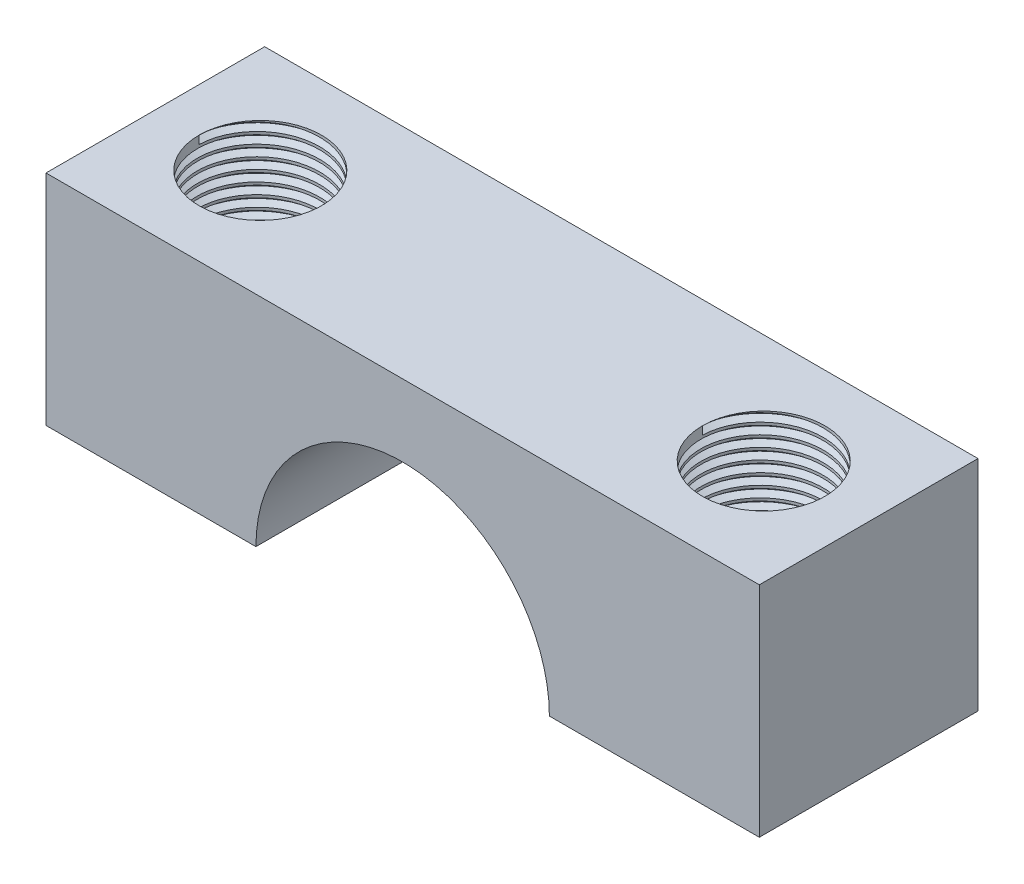
SolidWorks part; units mm, degrees
material "6061-T6 (SS)"
ref_plane "Front Plane" through (0, 0, 0) normal (0, 0, 1) x (1, 0, 0)
ref_plane "Top Plane" through (0, 0, 0) normal (0, 1, 0) x (1, 0, 0)
ref_plane "Right Plane" through (0, 0, 0) normal (1, 0, 0) x (0, 0, -1)
sketch "Sketch1" plane through (0, 0, 0) normal (0, 0, 1) x (1, 0, 0)
  line L1 (-8.155, -2.5) -> (8.155, -2.5)
  line L2 (-8.155, -2.5) -> (-8.155, 2.5)
  line L3 (-8.155, 2.5) -> (8.155, 2.5)
  line L4 (8.155, -2.5) -> (8.155, 2.5)
  line L5 (-8.155, -2.5) -> (8.155, 2.5) construction
  line L6 (-8.155, 2.5) -> (8.155, -2.5) construction
  point P0 (0, 0)
  dimension "D1" = 5
  dimension "D2" = 16.31
sketch "Sketch3" plane through (0, 0, 0) normal (0, 0, 1) x (1, 0, 0)
  line L0 (0, 0) -> (0, -2.5) construction
  line L1 (-8.155, -2.5) -> (8.155, -2.5) construction
  line L2 (-3.355, -2.5) -> (3.355, -2.5)
  line L3 (0, 0.855) -> (0, 2.5) construction
  line L4 (-8.155, 2.5) -> (8.155, 2.5) construction
  arc A0 (3.355, -2.5) -> (-3.355, -2.5) centre (0, -2.5) ccw
  point P8 (0, -2.5)
extrude "Boss-Extrude3" add sketch "Sketch1" against normal blind 5 contours L2 L3 L4 L1
extrude "Cut-Extrude9" cut sketch "Sketch3" against normal blind 5
sketch "Sketch4" plane through (0, 0, 0) normal (0, 1, 0) x (1, 0, 0)
  line L0 (0, 0) -> (0, 5) construction
  line L1 (-8.155, 0) -> (8.155, 0) construction
  line L2 (-8.155, 5) -> (8.155, 5) construction
  line L3 (0, 2.5) -> (5.755, 2.5) construction
  line L5 (0, 2.5) -> (-5.755, 2.5) construction
  circle A0 centre (-5.755, 2.5) radius 1.4
  circle A1 centre (5.755, 2.5) radius 1.4
extrude "Cut-Extrude10" cut sketch "Sketch4" against normal blind 2.5 and the other way blind 2.5 from offset 0
thread "Thread1" pitch 0.25 method cut profile "Thread Profile1" start angle 0, offset 0, length 5, pitch 0.25, diameter 2.8
ref_plane "Plane1" through (-7.155, 2.5, -2.5) normal (0, 0, 1) x (-1, 0, 0)
sketch "Thread Profile1" plane through (-7.155, 2.5, -2.5) normal (0, 0, 1) x (-1, 0, 0)
  line L0 (0, 0) -> (0, 0.25) construction
  line L1 (0, 0) -> (0.1353, 0.0781)
  line L2 (0.1353, 0.0781) -> (0.1353, 0.1094)
  line L3 (0.1353, 0.1094) -> (0, 0.1875)
  line L4 (0.1353, 0.0937) -> (0, 0.0937) construction
  line L11 (0, 0) -> (0, 0.1875)
  point P2 (0, 0)
  dimension "Pitch" = 0.25
  dimension "Profile_Angle" = 60
  dimension "Profile_Land" = 0.0312
  dimension "Profile_Height" = 0.1353
thread "Thread2" pitch 0.25 method cut profile "Thread Profile2" start angle 0, offset 0, length 5, pitch 0.25, diameter 2.8
ref_plane "Plane2" through (4.355, 2.5, -2.5) normal (0, 0, 1) x (-1, 0, 0)
sketch "Thread Profile2" plane through (4.355, 2.5, -2.5) normal (0, 0, 1) x (-1, 0, 0)
  line L0 (0, 0) -> (0, 0.25) construction
  line L1 (0, 0) -> (0.1353, 0.0781)
  line L2 (0.1353, 0.0781) -> (0.1353, 0.1094)
  line L3 (0.1353, 0.1094) -> (0, 0.1875)
  line L4 (0.1353, 0.0937) -> (0, 0.0937) construction
  line L11 (0, 0) -> (0, 0.1875)
  point P2 (0, 0)
  dimension "Pitch" = 0.25
  dimension "Profile_Angle" = 60
  dimension "Profile_Land" = 0.0312
  dimension "Profile_Height" = 0.1353
